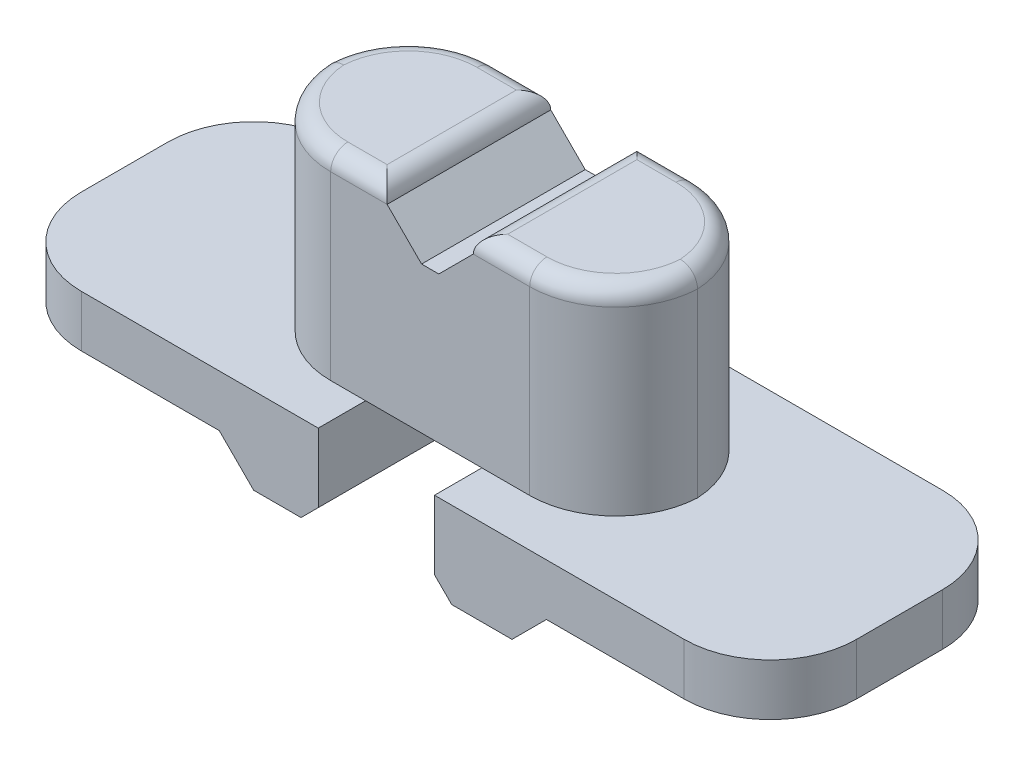
SolidWorks part; units mm, degrees
ref_plane "前视基准面" through (0, 0, 0) normal (0, 0, 1) x (1, 0, 0)
ref_plane "上视基准面" through (0, 0, 0) normal (0, 1, 0) x (1, 0, 0)
ref_plane "右视基准面" through (0, 0, 0) normal (1, 0, 0) x (0, 0, -1)
sketch "草图1" plane through (0, 0, 0) normal (0, 1, 0) x (1, 0, 0)
  line L1 (-4.0252, 1.9436) -> (4.9748, 1.9436)
  line L2 (-4.0252, 1.9436) -> (-4.0252, -1.0564)
  line L3 (-4.0252, -1.0564) -> (4.9748, -1.0564)
  line L4 (4.9748, 1.9436) -> (4.9748, -1.0564)
  line L5 (-4.0252, 1.9436) -> (4.9748, -1.0564) construction
  line L6 (-4.0252, -1.0564) -> (4.9748, 1.9436) construction
  point P0 (0.4748, 0.4436)
  dimension "D1" = 9
  dimension "D2" = 3
extrude "凸台-拉伸1" add sketch "草图1" along normal blind 0.6
sketch "草图2" plane through (0, 0.6, 0) normal (0, 1, 0) x (1, 0, 0)
  line L1 (-1.681, 1.3936) -> (2.6305, 1.3936)
  line L2 (-1.681, 1.3936) -> (-1.681, -0.5064)
  line L3 (-1.681, -0.5064) -> (2.6305, -0.5064)
  line L4 (2.6305, 1.3936) -> (2.6305, -0.5064)
  line L5 (-1.681, 1.3936) -> (2.6305, -0.5064) construction
  line L6 (-1.681, -0.5064) -> (2.6305, 1.3936) construction
  line L7 (4.9748, -1.0564) -> (4.9748, 1.9436) construction
  line L8 (4.9748, 1.9436) -> (-4.0252, 1.9436) construction
  point P0 (0.4748, 0.4436)
  point P12 (4.9748, 0.4436)
  point P17 (0.4748, 1.9436)
  dimension "D1" = 1.9
extrude "凸台-拉伸2" add sketch "草图2" along normal blind 2.3
fillet "圆角1" radius 1 8 edges at (-4.0252, 0.3, 1.0564) (-1.681, 1.75, 0.5064) (4.9748, 0.3, 1.0564) (2.6305, 1.75, 0.5064) (-1.681, 1.75, -1.3936) (2.6305, 1.75, -1.3936) (4.9748, 0.3, -1.9436) (-4.0252, 0.3, -1.9436)
sketch "草图3" plane through (0, 0, 0) normal (0, -1, 0) x (1, 0, 0)
  line L0 (3.9748, -1.9436) -> (-3.0252, -1.9436) construction
  line L1 (1.9748, -1.9436) -> (-1.0252, -1.9436)
  line L2 (1.9748, -1.9436) -> (1.9748, 1.0564)
  line L3 (1.9748, 1.0564) -> (-1.0252, 1.0564)
  line L4 (-1.0252, -1.9436) -> (-1.0252, 1.0564)
  line L5 (-3.0252, 1.0564) -> (3.9748, 1.0564) construction
  line L6 (4.9748, 0.0564) -> (4.9748, -0.9436) construction
  dimension "D1" = 3
  dimension "D2" = 3
extrude "凸台-拉伸3" add sketch "草图3" along normal blind 0.4
chamfer "倒角1" distance 0.4 angle 45 2 edges at (1.9748, 0, -0.4436) (-1.0252, 0, -0.4436)
sketch "草图5" plane through (0, 0, -1.9436) normal (0, 0, -1) x (-1, 0, 0)
  line L1 (0.2752, -0.4) -> (-1.0748, -0.4)
  line L2 (0.2752, -0.4) -> (0.2752, 0.6)
  line L3 (0.2752, 0.6) -> (-1.0748, 0.6)
  line L4 (-1.0748, -0.4) -> (-1.0748, 0.6)
  line L5 (-4.9748, 0) -> (-4.9748, 0.6) construction
  line L6 (1.0252, -0.4) -> (-1.9748, -0.4) construction
  dimension "D1" = 1.35
  dimension "D2" = 3.9
  dimension "D3" = 1
extrude "切除-拉伸1" cut sketch "草图5" against normal up to next
chamfer "倒角2" distance 0.2 angle 45 2 edges at (1.0748, -0.4, -0.4436) (-0.2752, -0.4, -0.4436)
sketch "草图7" plane through (0, 0, 0.5064) normal (0, 0, 1) x (1, 0, 0)
  line L0 (-0.681, 2.9) -> (1.6305, 2.9) construction
  line L1 (0.9748, 2.3) -> (-0.0252, 2.3)
  line L2 (0.9748, 2.3) -> (0.9748, 2.9)
  line L3 (0.9748, 2.9) -> (-0.0252, 2.9)
  line L4 (-0.0252, 2.3) -> (-0.0252, 2.9)
  line L5 (0.9748, 2.3) -> (-0.0252, 2.9) construction
  line L6 (0.9748, 2.9) -> (-0.0252, 2.3) construction
  point P0 (0.4748, 2.6)
  dimension "D1" = 1
extrude "切除-拉伸2" cut sketch "草图7" against normal up to next and the other way through all
chamfer "倒角3" distance 0.4 angle 45 2 edges at (0.9748, 2.3, -0.4436) (-0.0252, 2.3, -0.4436)
fillet "圆角2" radius 0.2 10 edges at (-1.3702, 2.9, 0.2309) (-1.3702, 2.9, -1.1182) (-0.3531, 2.9, -1.3936) (-0.3531, 2.9, 0.5064) (2.3197, 2.9, -1.1182) (2.3197, 2.9, 0.2309) (1.3026, 2.9, 0.5064) (1.3026, 2.9, -1.3936) (-0.0252, 2.9, -0.4436) (0.9748, 2.9, -0.4436)
